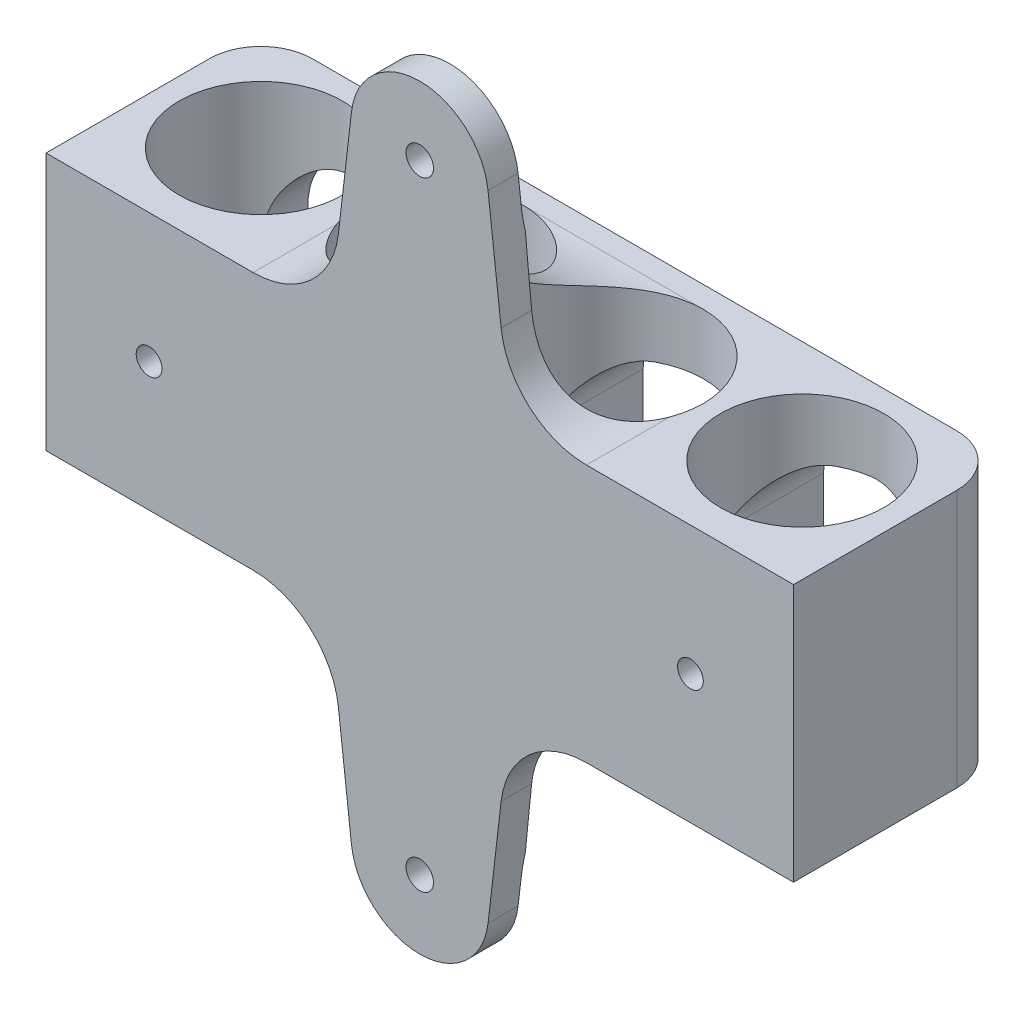
SolidWorks part; units mm, degrees
ref_plane "Front Plane" through (0, 0, 0) normal (0, 0, 1) x (1, 0, 0)
ref_plane "Top Plane" through (0, 0, 0) normal (0, 1, 0) x (1, 0, 0)
ref_plane "Right Plane" through (0, 0, 0) normal (1, 0, 0) x (0, 0, -1)
sketch "Sketch1" plane through (0, 0, 0) normal (0, 1, 0) x (1, 0, 0)
  line L0 (0, 0) -> (52.2087, 0) construction
  line L2 (-12, 12) -> (75, 12)
  line L3 (-12, 12) -> (-12, -13)
  line L4 (-12, -13) -> (75, -13)
  line L5 (75, 12) -> (75, -13)
  circle A0 centre (0, 0) radius 9.5
  circle A1 centre (21, 0) radius 9.5
  circle A2 centre (42, 0) radius 9.5
  circle A3 centre (63, 0) radius 9.5
  dimension "D1" = 19
  dimension "D2" = 19
  dimension "D3" = 19
  dimension "D4" = 19
  dimension "D6" = 21
  dimension "D7" = 21
  dimension "D11" = 12
  dimension "D5" = 21
  dimension "D8" = 12
  dimension "D9" = 13
  dimension "D10" = 12
extrude "Boss-Extrude1" add sketch "Sketch1" along normal blind 30
sketch "Sketch10" plane through (0, 0, 13) normal (0, 0, 1) x (1, 0, 0)
  line L0 (31.5, 30) -> (31.5, 51) construction
  line L1 (-12, 30) -> (75, 30) construction
  line L2 (39.4463, 51.9255) -> (42, 30)
  line L3 (23.5537, 51.9255) -> (21, 30)
  line L4 (21, 30) -> (42, 30)
  line L5 (-12, 15) -> (75, 15) construction
  line L6 (-12, 30) -> (-12, 0) construction
  line L7 (75, 30) -> (75, 0) construction
  line L8 (31.5, 0) -> (31.5, -21) construction
  line L9 (21, 0) -> (42, 0)
  line L10 (23.5537, -21.9255) -> (21, 0)
  line L11 (39.4463, -21.9255) -> (42, 0)
  line L12 (75, 30) -> (-12, 30) construction
  circle A0 centre (31.5, 51) radius 1.6
  arc A1 (39.4463, 51.9255) -> (23.5537, 51.9255) centre (31.5, 51) ccw
  arc A2 (39.4463, -21.9255) -> (23.5537, -21.9255) centre (31.5, -21) cw
  circle A3 centre (31.5, -21) radius 1.6
  dimension "D2" = 16
  dimension "D3" = 3.2
  dimension "D1" = 21
  dimension "D4" = 10.5
  dimension "D5" = 10.5
extrude "Boss-Extrude4" add sketch "Sketch10" against normal blind 3.5
fillet "Fillet3" radius 19 2 edges at (31.5, 30, 9.5) (31.5, 0, 9.5)
fillet "Fillet4" radius 6 2 edges at (-12, 15, -12) (75, 15, -12)
fillet "Fillet5" radius 10 4 edges at (42, 0, 11.25) (21, 0, 11.25) (21, 30, 11.25) (42, 30, 11.25)
sketch "Sketch11" plane through (0, 0, 13) normal (0, 0, 1) x (1, 0, 0)
  line L0 (-12, 15) -> (75, 15) construction
  line L1 (-12, 30) -> (-12, 0) construction
  line L2 (75, 30) -> (75, 0) construction
  line L3 (31.5, 15) -> (31.5, 60.7131) construction
  line L5 (-9.5, 30) -> (-9.5, 0) construction
  circle A0 centre (0, 15) radius 1.5
  circle A2 centre (63, 15) radius 1.5
  dimension "D1" = 3
  dimension "D2" = 9.5
extrude "Cut-Extrude5" cut sketch "Sketch11" against normal blind 13.5
sketch "Sketch12" plane through (0, 0, -12) normal (0, 0, -1) x (-1, 0, 0)
  line L0 (-61.5, 15) -> (-1.5, 15) construction
  line L1 (-61.5, 23) -> (-1.5, 23)
  line L2 (-61.5, 7) -> (-1.5, 7)
  line L3 (-61.5, 15) -> (-75, 15) construction
  line L4 (-75, 0) -> (-75, 30) construction
  line L5 (-31.5, 15) -> (-31.5, 30) construction
  line L6 (-21, 30) -> (-42, 30) construction
  line L7 (-53.5, 0) -> (-53.5, 30) construction
  line L8 (-53.5, 7) -> (-53.5, 23)
  line L9 (-51.5, 30) -> (-51.5, 0) construction
  line L10 (-51.5, 23) -> (-51.5, 7)
  line L11 (-32.5, -2.5456) -> (-32.5, 32.5455) construction
  line L12 (-32.5, 7) -> (-32.5, 23)
  line L13 (-30.5, 32.5456) -> (-30.5, -2.5456) construction
  line L14 (-30.5, 23) -> (-30.5, 7)
  line L15 (-11.5, 0) -> (-11.5, 30) construction
  line L16 (-11.5, 7) -> (-11.5, 23)
  line L17 (-9.5, 30) -> (-9.5, 0) construction
  line L18 (-9.5, 23) -> (-9.5, 7)
  arc A0 (-61.5, 23) -> (-61.5, 7) centre (-61.5, 15) ccw
  arc A1 (-1.5, 7) -> (-1.5, 23) centre (-1.5, 15) ccw
  point P2 (-31.5, 15)
  line M9 (6, 0) -> (6, 30)
  line M11 (-69, 30) -> (-69, 0)
  dimension "D1" = 8
  dimension "D2" = 60
extrude "Cut-Extrude6" cut sketch "Sketch12" against normal blind 12 contours A1 M9 | A1 L1 L18 L2 M9 | L2 L16 L1 L14 | L2 L12 L1 L10 | L1 A0 L2 L8 M11 | A0 M11
fillet "Fillet7" radius 5 12 edges at (9.5, 23, -6) (30.5, 23, -6) (51.5, 23, -6) (53.5, 23, -6) (32.5, 23, -6) (11.5, 23, -6) (11.5, 7, -6) (32.5, 7, -6) (9.5, 7, -6) (30.5, 7, -6) (51.5, 7, -6) (53.5, 7, -6)
sketch "Sketch13" plane through (0, 0, 9.5) normal (0, 0, -1) x (-1, 0, 0)
  line L0 (-31.5, -21) -> (-31.5, 51) construction
  line L1 (-28.3246, 51) -> (-29.9123, 53.75)
  line L2 (-29.9123, 53.75) -> (-33.0877, 53.75)
  line L3 (-33.0877, 53.75) -> (-34.6754, 51)
  line L4 (-34.6754, 51) -> (-33.0877, 48.25)
  line L5 (-33.0877, 48.25) -> (-29.9123, 48.25)
  line L6 (-29.9123, 48.25) -> (-28.3246, 51)
  line L7 (-31.5, 15) -> (12, 15) construction
  line L8 (12, 30) -> (12, 0) construction
  line L9 (-29.9123, -18.25) -> (-28.3246, -21)
  line L10 (-33.0877, -18.25) -> (-29.9123, -18.25)
  line L11 (-34.6754, -21) -> (-33.0877, -18.25)
  line L12 (-33.0877, -23.75) -> (-34.6754, -21)
  line L13 (-29.9123, -23.75) -> (-33.0877, -23.75)
  line L14 (-28.3246, -21) -> (-29.9123, -23.75)
  circle A0 centre (-31.5, 51) radius 2.75 construction
  circle A1 centre (-31.5, 51) radius 5
  circle A2 centre (-31.5, -21) radius 2.75 construction
  circle A3 centre (-31.5, -21) radius 5
  dimension "D1" = 5.5
  dimension "D2" = 10
extrude "Boss-Extrude5" add sketch "Sketch13" along normal blind 2
fillet "Fillet8" radius 2 4 edges at (31.395, -25.9989, 8.164) (32.7213, 46.1514, 9.2853) (31.5, -26, 9.5) (31.5, 56, 9.5)
